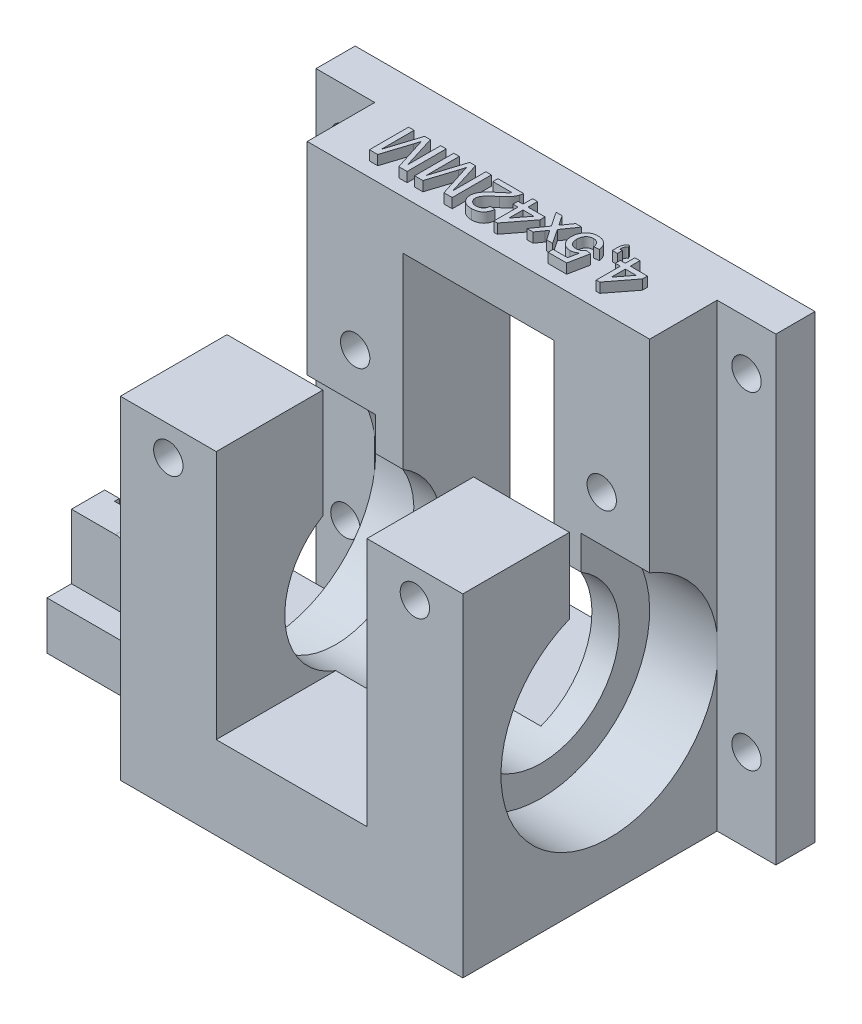
SolidWorks part; units mm, degrees
ref_plane "Спереди" through (0, 0, 0) normal (0, 0, 1) x (1, 0, 0)
ref_plane "Сверху" through (0, 0, 0) normal (0, 1, 0) x (1, 0, 0)
ref_plane "Справа" through (0, 0, 0) normal (1, 0, 0) x (0, 0, -1)
sketch "Эскиз1" plane through (0, 0, 0) normal (0, 1, 0) x (1, 0, 0)
  line L1 (17.5, -15) -> (-17.5, -15)
  line L2 (17.5, -15) -> (17.5, 15)
  line L3 (17.5, 15) -> (-17.5, 15)
  line L4 (-17.5, -15) -> (-17.5, 15)
  line L5 (17.5, -15) -> (-17.5, 15) construction
  line L6 (17.5, 15) -> (-17.5, -15) construction
  point P0 (0, 0)
  dimension "D1" = 35
  dimension "D2" = 30
extrude "Бобышка-Вытянуть1" add sketch "Эскиз1" along normal blind 42
sketch "Эскиз2" plane through (0, 42, 0) normal (0, 1, 0) x (1, 0, 0)
  line L0 (17.5, 15) -> (-17.5, 15) construction
  line L1 (7.7, -15) -> (-7.7, -15)
  line L2 (7.7, -15) -> (7.7, 15)
  line L3 (7.7, 15) -> (-7.7, 15)
  line L4 (-7.7, -15) -> (-7.7, 15)
  line L5 (7.7, -15) -> (-7.7, 15) construction
  line L6 (7.7, 15) -> (-7.7, -15) construction
  point P0 (0, 0)
  dimension "D1" = 9.8
  dimension "D2" = 15.4
extrude "Вырез-Вытянуть1" cut sketch "Эскиз2" against normal blind 33.5
sketch "Эскиз3" plane through (-17.5, 0, 0) normal (-1, 0, 0) x (0, 0, 1)
  line L0 (15, 16) -> (-15, 16) construction
  line L2 (15, 42) -> (15, 0) construction
  line L3 (-15, 42) -> (-15, 0) construction
  line L4 (-15, 0) -> (15, 0) construction
  circle A0 centre (0, 16) radius 11.1
  point P11 (0, 16)
  point P15 (0, 0)
  dimension "D1" = 22.2
  dimension "D2" = 16
extrude "Вырез-Вытянуть2" cut sketch "Эскиз3" against normal blind 7
sketch "Эскиз4" plane through (17.5, 0, 0) normal (1, 0, 0) x (0, 0, -1)
  line L0 (-15, 16) -> (15, 16) construction
  line L3 (-15, 42) -> (-15, 0) construction
  line L4 (15, 42) -> (15, 0) construction
  circle A0 centre (0, 16) radius 11.1
  dimension "D1" = 22.2
  dimension "D2" = 16
extrude "Вырез-Вытянуть3" cut sketch "Эскиз4" against normal blind 7
sketch "Эскиз5" plane through (-10.5, 0, 0) normal (-1, 0, 0) x (0, 0, 1)
  circle A0 centre (0, 16) radius 8
  dimension "D1" = 16
extrude "Вырез-Вытянуть4" cut sketch "Эскиз5" against normal through all
sketch "Эскиз6" plane through (0, 42, 0) normal (0, 1, 0) x (1, 0, 0)
  line L0 (17.5, -15) -> (17.5, 15) construction
  line L1 (-17.5, 4.1) -> (17.5, 4.1)
  line L2 (-17.5, 4.1) -> (-17.5, -4.1)
  line L3 (-17.5, -4.1) -> (17.5, -4.1)
  line L4 (17.5, 4.1) -> (17.5, -4.1)
  line L5 (-17.5, 4.1) -> (17.5, -4.1) construction
  line L6 (-17.5, -4.1) -> (17.5, 4.1) construction
  point P0 (0, 0)
  dimension "D1" = 8.2
extrude "Вырез-Вытянуть5" cut sketch "Эскиз6" against normal blind 20
sketch "Эскиз7" plane through (0, 0, -15) normal (0, 0, -1) x (-1, 0, 0)
  line L0 (-17.5, 31) -> (-7.7, 31) construction
  line L1 (-17.5, 42) -> (-17.5, 0) construction
  line L2 (-7.7, 8.5) -> (-7.7, 42) construction
  line L3 (7.7, 31) -> (17.5, 31) construction
  line L4 (7.7, 8.5) -> (7.7, 42) construction
  line L5 (17.5, 42) -> (17.5, 0) construction
  line L6 (-17.5, 42) -> (-7.7, 42) construction
  circle A0 centre (-12.6, 31) radius 1.5
  circle A1 centre (12.6, 31) radius 1.5
  point P12 (-12.6, 31)
  point P15 (-12.6, 42)
  dimension "D2" = 3
  dimension "D1" = 11
extrude "Вырез-Вытянуть6" cut sketch "Эскиз7" against normal through all
sketch "Эскиз9" plane through (-17.5, 0, 0) normal (1, 0, 0) x (0, 0, -1)
  line L0 (-15, 2.45) -> (15, 2.45) construction
  line L1 (-15, 42) -> (-15, 0) construction
  line L2 (15, 42) -> (15, 0) construction
  line L3 (0, 4.9) -> (0, 0) construction
  line L4 (-15, 0) -> (15, 0) construction
  line L6 (7.5, 0) -> (-7.5, 0)
  line L7 (7.5, 0) -> (7.5, 4.9)
  line L8 (7.5, 4.9) -> (-7.5, 4.9)
  line L9 (-7.5, 0) -> (-7.5, 4.9)
  line L10 (7.5, 0) -> (-7.5, 4.9) construction
  line L11 (7.5, 4.9) -> (-7.5, 0) construction
  circle A0 centre (0, 16) radius 11.1 construction
  point P13 (0, 2.45)
  point P14 (0, 2.45)
  point P15 (0, 2.45)
  dimension "D1" = 15
  dimension "D2" = 4.9
extrude "Бобышка-Вытянуть2" add sketch "Эскиз9" against normal blind 15
sketch "Эскиз10" plane through (0, 4.9, 0) normal (0, 1, 0) x (1, 0, 0)
  line L0 (-29.5, 7.5) -> (-29.5, -7.5) construction
  line L1 (-32.5, 7.5) -> (-17.5, 7.5) construction
  line L2 (-32.5, -7.5) -> (-17.5, -7.5) construction
  line L3 (-32.5, 7.5) -> (-32.5, -7.5) construction
  line L4 (-26.5, -5) -> (-32.5, -5)
  line L5 (-26.5, -5) -> (-26.5, 5)
  line L6 (-26.5, 5) -> (-32.5, 5)
  line L7 (-32.5, -5) -> (-32.5, 5)
  line L8 (-26.5, -5) -> (-32.5, 5) construction
  line L9 (-26.5, 5) -> (-32.5, -5) construction
  point P6 (-29.5, 0)
  point P13 (-32.5, 0)
  dimension "D1" = 10
  dimension "D2" = 3
extrude "Бобышка-Вытянуть3" add sketch "Эскиз10" along normal blind 6.6
sketch "Эскиз11" plane through (0, 11.5, 0) normal (0, 1, 0) x (1, 0, 0)
  line L0 (-26.5, 0) -> (-32.5, 0) construction
  line L1 (-26.5, -5) -> (-26.5, 5) construction
  line L2 (-32.5, 5) -> (-32.5, -5) construction
  line L3 (-31, 1.6) -> (-32.5, 1.6)
  line L4 (-31, -2.1) -> (-28, -2.1)
  line L5 (-31, 1.6) -> (-31, 2.1)
  line L6 (-31, 2.1) -> (-28, 2.1)
  line L7 (-28, -2.1) -> (-28, 2.1)
  line L8 (-31, -2.1) -> (-28, 2.1) construction
  line L9 (-31, 2.1) -> (-28, -2.1) construction
  line L10 (-32.5, 1.6) -> (-32.5, -1.6)
  line L11 (-32.5, -1.6) -> (-31, -1.6)
  line L12 (-31, -1.6) -> (-31, -2.1)
  point P6 (-29.5, 0)
  dimension "D1" = 4.2
  dimension "D2" = 3
  dimension "D3" = 3.2
extrude "Вырез-Вытянуть8" cut sketch "Эскиз11" against normal blind 1.3
sketch "Эскиз12" plane through (-32.5, 0, 0) normal (-1, 0, 0) x (0, 0, 1)
  line L0 (0, 10.2) -> (0, 0) construction
  line L1 (-1.6, 10.2) -> (1.6, 10.2) construction
  line L2 (7.5, 0) -> (-7.5, 0) construction
  line L4 (1.6, 0) -> (-1.6, 0)
  line L5 (1.6, 0) -> (1.6, 10.2)
  line L6 (1.6, 10.2) -> (-1.6, 10.2)
  line L7 (-1.6, 0) -> (-1.6, 10.2)
  line L8 (1.6, 0) -> (-1.6, 10.2) construction
  line L9 (1.6, 10.2) -> (-1.6, 0) construction
  point P6 (0, 5.1)
extrude "Вырез-Вытянуть9" cut sketch "Эскиз12" against normal blind 1
sketch "Эскиз13" plane through (-17.5, 0, 0) normal (-1, 0, 0) x (0, 0, 1)
  line L0 (-11.1, 16) -> (11.1, 16) construction
  line L1 (0, 16) -> (0, 0) construction
  circle A0 centre (0, 16) radius 11.1 construction
  circle A1 centre (0, 16) radius 11.1 construction
  dimension "D1" = 16
sketch "Эскиз14" plane through (0, 42, 0) normal (0, 1, 0) x (1, 0, 0)
  line L0 (17.5, 9.55) -> (-17.5, 9.55) construction
  line L1 (17.5, 4.1) -> (17.5, 15) construction
  line L2 (-17.5, 15) -> (-17.5, 4.1) construction
  line L4 (-17.5, 15) -> (17.5, 15)
  line L5 (-17.5, 15) -> (-17.5, 4.1)
  line L6 (-17.5, 4.1) -> (17.5, 4.1)
  line L7 (17.5, 15) -> (17.5, 4.1)
  line L8 (-17.5, 15) -> (17.5, 4.1) construction
  line L9 (-17.5, 4.1) -> (17.5, 15) construction
  point P6 (0, 9.55)
extrude "Бобышка-Вытянуть4" add sketch "Эскиз14" along normal blind 5
sketch "Эскиз15" plane through (0, 42, 0) normal (0, 1, 0) x (1, 0, 0)
  line L0 (-7.7, -4.1) -> (-17.5, -15) construction
  line L1 (17.5, -4.1) -> (7.7, -15) construction
  line L3 (-17.5, -15) -> (-7.7, -15)
  line L4 (-17.5, -15) -> (-17.5, -4.1)
  line L5 (-17.5, -4.1) -> (-7.7, -4.1)
  line L6 (-7.7, -15) -> (-7.7, -4.1)
  line L7 (-17.5, -15) -> (-7.7, -4.1) construction
  line L8 (-17.5, -4.1) -> (-7.7, -15) construction
  line L9 (7.7, -15) -> (17.5, -15)
  line L10 (7.7, -15) -> (7.7, -4.1)
  line L11 (7.7, -4.1) -> (17.5, -4.1)
  line L12 (17.5, -15) -> (17.5, -4.1)
  line L13 (7.7, -15) -> (17.5, -4.1) construction
  line L14 (7.7, -4.1) -> (17.5, -15) construction
  point P8 (-12.6, -9.55)
  point P9 (12.6, -9.55)
extrude "Вырез-Вытянуть10" cut sketch "Эскиз15" against normal blind 8
sketch "Эскиз17" plane through (0, 47, 0) normal (0, 1, 0) x (1, 0, 0)
  line L0 (17.5, 9.55) -> (-17.5, 9.55) construction
  line L1 (17.5, 4.1) -> (17.5, 15) construction
  line L2 (-17.5, 15) -> (-17.5, 4.1) construction
  text T0 "4,5x42MM"
extrude "Бобышка-Вытянуть5" add sketch "Эскиз17" along normal blind 1
sketch "Эскиз23" plane through (17.5, 0, 0) normal (1, 0, 0) x (0, 0, -1)
  line L0 (13, 47) -> (13, 0) construction
  line L1 (4.1, 47) -> (15, 47) construction
  line L2 (-15, 0) -> (15, 0) construction
  line L4 (11, 0) -> (15, 0)
  line L5 (11, 0) -> (11, 47)
  line L6 (11, 47) -> (15, 47)
  line L7 (15, 0) -> (15, 47)
  line L8 (11, 0) -> (15, 47) construction
  line L9 (11, 47) -> (15, 0) construction
  point P6 (13, 23.5)
  dimension "D1" = 2
extrude "Бобышка-Вытянуть7" add sketch "Эскиз23" along normal blind 6
sketch "Эскиз25" plane through (-17.5, 0, 0) normal (-1, 0, 0) x (0, 0, 1)
  line L0 (-13, 47) -> (-13, 0) construction
  line L1 (-15, 47) -> (-4.1, 47) construction
  line L2 (-15, 0) -> (-7.5, 0) construction
  line L4 (-11, 0) -> (-15, 0)
  line L5 (-11, 0) -> (-11, 47)
  line L6 (-11, 47) -> (-15, 47)
  line L7 (-15, 0) -> (-15, 47)
  line L8 (-11, 0) -> (-15, 47) construction
  line L9 (-11, 47) -> (-15, 0) construction
  point P6 (-13, 23.5)
  dimension "D1" = 2
extrude "Бобышка-Вытянуть8" add sketch "Эскиз25" along normal blind 6
sketch "Эскиз26" plane through (0, 0, -15) normal (0, 0, -1) x (-1, 0, 0)
  line L0 (-20.5, 42) -> (-20.5, 8.5) construction
  line L1 (-7.7, 42) -> (7.7, 42) construction
  line L2 (23.5, 47) -> (23.5, 0) construction
  line L5 (-20.5, 8.5) -> (20.5, 8.5) construction
  line L6 (20.5, 8.5) -> (20.5, 42) construction
  line L7 (20.5, 42) -> (-20.5, 42) construction
  circle A0 centre (-20.5, 42) radius 1.5
  circle A1 centre (-20.5, 8.5) radius 1.5
  circle A2 centre (20.5, 42) radius 1.5
  circle A3 centre (20.5, 8.5) radius 1.5
  point P4 (0, 42)
  point P7 (0, 42)
  dimension "D3" = 3
  dimension "D1" = 3
  dimension "D4" = 41
extrude "Вырез-Вытянуть12" cut sketch "Эскиз26" against normal through all
sketch "Эскиз27" plane through (0, 0, -15) normal (0, 0, -1) x (-1, 0, 0)
  circle A0 centre (12.6, 31) radius 3
  circle A1 centre (-12.6, 31) radius 3
  dimension "D1" = 6
extrude "Вырез-Вытянуть13" cut sketch "Эскиз27" against normal blind 3
fillet "Fillet1" radius 1.5 1 edges at (-26.5, 11.5, 0)
